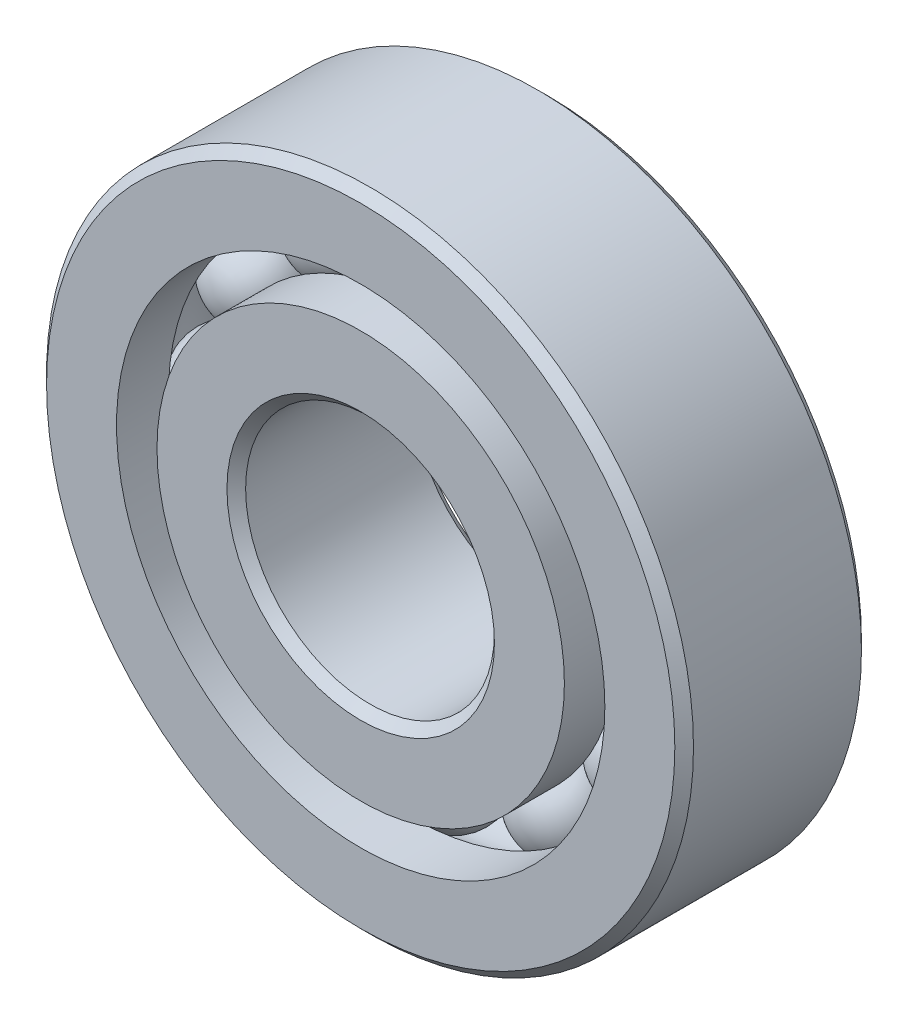
SolidWorks part; units mm, degrees
material "AISI 4130 Steel, normalized at 870C"
ref_plane "Front Plane" through (0, 0, 0) normal (0, 0, 1) x (1, 0, 0)
ref_plane "Top Plane" through (0, 0, 0) normal (0, 1, 0) x (1, 0, 0)
ref_plane "Right Plane" through (0, 0, 0) normal (1, 0, 0) x (0, 0, -1)
sketch "Sketch1" plane through (0, 0, 0) normal (1, 0, 0) x (0, 0, -1)
  line L0 (-7.5, 0) -> (7.5, 0) construction
  line L1 (0, 26) -> (0, -26) construction
  line L2 (6.75, 26) -> (-6.75, 26)
  line L3 (-6.75, 26) -> (-7.5, 25.25)
  line L4 (-7.5, 25.25) -> (-7.5, 19.6264)
  line L5 (-7.5, 19.6264) -> (-3.3333, 19.6264)
  line L6 (7.5, 19.6264) -> (3.3333, 19.6264)
  line L7 (7.5, 25.25) -> (7.5, 19.6264)
  line L8 (6.75, 26) -> (7.5, 25.25)
  line L9 (0, 26) -> (0, 18) construction
  line L10 (0, 18) -> (0, 10) construction
  arc A0 (-3.3333, 19.6264) -> (3.3333, 19.6264) centre (0, 18) cw
  point P14 (0, 10)
  dimension "D3" = 6.6667
  dimension "D1" = 45
  dimension "Width" = 15
  dimension "OD" = 52
  dimension "D2" = 0.75
  dimension "Shaft Dia" = 20
  dimension "D4" = 1.6264
revolve "Revolve1" add sketch "Sketch1" angle 360 about L0
sketch "Sketch3" plane through (0, 0, 0) normal (1, 0, 0) x (0, 0, -1)
  line L0 (-7.5, 16.3736) -> (-3.3333, 16.3736)
  line L1 (0, 26) -> (0, -26) construction
  line L2 (-7.5, 25.25) -> (-7.5, 19.6264) construction
  line L3 (-7.5, 16.3736) -> (-7.5, 10.75)
  line L4 (-6.75, 26) -> (-7.5, 25.25) construction
  line L5 (-7.5, 10.75) -> (-6.75, 10)
  line L6 (-6.75, 10) -> (6.75, 10)
  line L7 (6.75, 26) -> (6.75, -26) construction
  line L8 (6.75, 10) -> (7.5, 10.75)
  line L9 (7.5, -25.25) -> (7.5, 25.25) construction
  line L10 (7.5, 10.75) -> (7.5, 16.3736)
  line L11 (7.5, 16.3736) -> (3.3333, 16.3736)
  line L13 (6.75, 26) -> (7.5, 25.25) construction
  arc A0 (3.3333, 19.6264) -> (-3.3333, 19.6264) centre (0, 18) ccw construction
  arc A1 (3.3333, 16.3736) -> (-3.3333, 16.3736) centre (0, 18) cw
revolve "Revolve3" add sketch "Sketch3" angle 360 about L0
sketch "Sketch4" plane through (0, 0, 0) normal (1, 0, 0) x (0, 0, -1)
  line L0 (-3.7089, 18) -> (3.7089, 18)
  arc A2 (-3.7089, 18) -> (3.7089, 18) centre (0, 18) cw
  arc A3 (3.3333, 19.6264) -> (-3.3333, 19.6264) centre (0, 18) ccw construction
revolve "Revolve4" add sketch "Sketch4" angle 360 about L0
ref_axis "Axis1" through (0, 0, -7.5) along (0, 0, 1)
pattern_circular "CirPattern1" count 12 every 30 about axis through (0, 0, -7.5) along (0, 0, 1) of bodies 104
sketch "Sketch5" plane through (0, 0, 0) normal (1, 0, 0) x (0, 0, -1)
  line L0 (-7.5, 19.6264) -> (-3.3333, 19.6264) construction
  line L1 (-7.125, 19.6264) -> (-3.7089, 19.6264)
  line L2 (-7.125, 19.6264) -> (-7.125, 16.3736)
  line L3 (-7.125, 16.3736) -> (-3.7089, 16.3736)
  line L4 (-3.7089, 19.6264) -> (-3.7089, 16.3736)
  line L5 (-7.5, 16.3736) -> (-3.3333, 16.3736) construction
  line L6 (7.5, 19.6264) -> (3.3333, 19.6264) construction
  line L7 (7.125, 19.6264) -> (3.7089, 19.6264)
  line L8 (7.125, 19.6264) -> (7.125, 16.3736)
  line L9 (7.125, 16.3736) -> (3.7089, 16.3736)
  line L10 (3.7089, 19.6264) -> (3.7089, 16.3736)
  line L11 (7.5, 16.3736) -> (3.3333, 16.3736) construction
  line L12 (-6.75, 26) -> (-7.5, 25.25) construction
  point P18 (-7.125, 25.625)
revolve "Revolve5" [suppressed] add sketch "Sketch5" angle 360 about L0
equation "\"D2@Sketch1\" = \"Width@Sketch1\"*.05"
equation "\"D3@Sketch1\" = \"Width@Sketch1\"/2.25"
equation "\"D4@Sketch1\" = (((\"OD@Sketch1\"-\"Width@Sketch1\")/2)/3.25)/3.5"
equation "\"D2@CirPattern1\" = 360/\"Balls@CirPattern1\""
